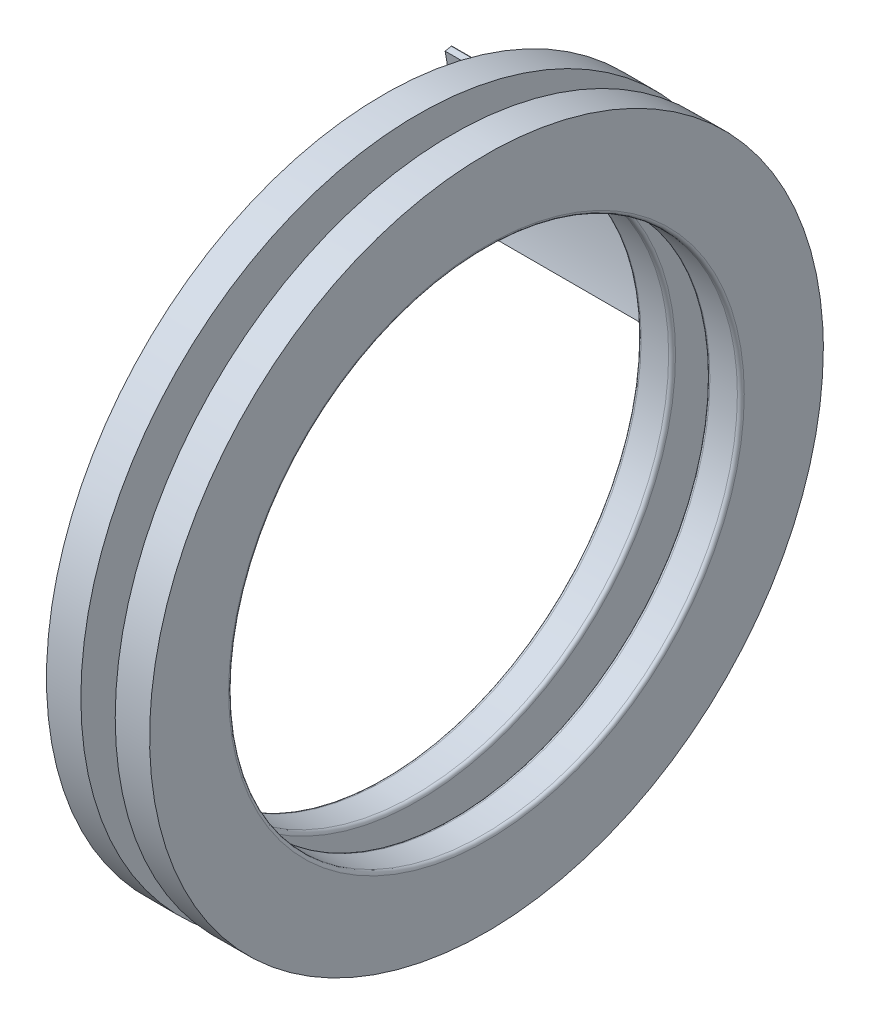
SolidWorks part; units mm, degrees
ref_plane "Front Plane" through (0, 0, 0) normal (0, 0, 1) x (1, 0, 0)
ref_plane "Top Plane" through (0, 0, 0) normal (0, 1, 0) x (1, 0, 0)
ref_plane "Right Plane" through (0, 0, 0) normal (1, 0, 0) x (0, 0, -1)
sketch "airflap" plane through (0, 0, 0) normal (1, 0, 0) x (0, 0, -1)
  line L0 (0, 0) -> (0, 50) construction
  line L1 (0, 0) -> (0, -50) construction
  line L2 (49.9696, 10.2) -> (48.9898, 10)
  line L3 (-48.9898, -10) -> (48.9898, -10) construction
  line L4 (-48.9898, -10) -> (-48.9898, 10) construction
  line L5 (-48.9898, 10) -> (48.9898, 10) construction
  line L6 (48.9898, -10) -> (48.9898, 10) construction
  line L7 (-48.9898, -10) -> (48.9898, 10) construction
  line L8 (-48.9898, 10) -> (48.9898, -10) construction
  line L9 (48.9898, -10) -> (49.9696, -10.2)
  arc A0 (48.9898, 10) -> (48.9898, -10) centre (0, 0) cw
  arc A1 (49.9696, 10.2) -> (49.9696, -10.2) centre (0, 0) cw
  dimension "D2" = 20
  dimension "D3" = 50
  dimension "D4" = 51
  dimension "D1" = 50
extrude "Boss-Extrude1" add sketch "airflap" along normal blind 50
fillet "Fillet3" radius 0.1 5 edges at (50, 10.1, -49.4797) (50, -10.1, -49.4797) (25, -10.2, -49.9696) (25, 10.2, -49.9696) (50, 0, -51)
ref_plane "hinge sketch" through (50, 0, 0) normal (1, 0, 0) x (0, 0, -1)
sketch "inner-hinge" plane through (50, 0, 0) normal (1, 0, 0) x (0, 0, -1)
  line L0 (49.0097, 9.902) -> (49.0097, -9.902) construction
  line L1 (49.0097, 0) -> (50, 0) construction
  line L2 (49.0097, 3) -> (42.0097, 3)
  line L4 (49.0097, -3) -> (42.0097, -3)
  line L5 (42.0097, 3) -> (42.0097, -3)
  line L6 (49.0097, 3) -> (49.9099, 3)
  line L8 (49.0097, -3) -> (49.9099, -3)
  line L9 (49.0097, 0) -> (42.0097, 0) construction
  arc A0 (49.0097, -9.902) -> (49.0097, 9.902) centre (0, 0) ccw construction
  arc A1 (49.9099, 3) -> (49.9099, -3) centre (0, 0) cw
  dimension "D1" = 6
  dimension "D2" = 42.0097
  dimension "D3" = 7
  dimension "D5" = 0.9903
extrude "Boss-Extrude2" add sketch "inner-hinge" against normal blind 5 separate body
ref_plane "inner-screw hinge" through (0, 0, 0) normal (0, 1, 0) x (1, 0, 0)
sketch "cutout-hinge" plane through (0, 0, 0) normal (0, 1, 0) x (1, 0, 0)
  line L0 (47.5, 42.0097) -> (47.5, 50) construction
  line L1 (45, 42.0097) -> (50, 42.0097) construction
  line L2 (45, 42.0097) -> (50, 42.0097) construction
  line L3 (45, 42.0097) -> (45, 49.9099) construction
  line L4 (50, 42.0097) -> (45, 42.0097)
  line L5 (50, 42.0097) -> (50, 48.9898)
  line L6 (50, 48.9898) -> (45, 48.9898)
  line L7 (45, 42.0097) -> (45, 48.9898)
  line L8 (49.9, 48.9898) -> (0, 48.9898) construction
  circle A0 centre (47.5, 46.0048) radius 2
  circle A1 centre (47.5, 46.0048) radius 2.5
  dimension "D1" = 4
  dimension "D2" = 7.9903
  dimension "D3" = 3.9952
  dimension "D4" = 0.5
fillet "Fillet4" radius 0.5 2 edges at (50, 0, -42.0097) (45, 0, -42.0097)
sketch "set ring" plane through (50, 0, 0) normal (1, 0, 0) x (0, 0, -1)
  circle A0 centre (0, 0) radius 49.0097
  circle A1 centre (0, 0) radius 37.0097
  dimension "D1" = 12
extrude "setring" add sketch "set ring" along normal blind 5
ref_plane "mirrorplane" through (47.5, 0, 0) normal (1, 0, 0) x (0, 0, -1)
mirror "Mirror1" about plane through (47.5, 0, 0) normal (1, 0, 0) of "setring"
fillet "Fillet5" radius 0.5 4 edges at (40, 0, -37.0097) (45, 0, -37.0097) (50, 0, -37.0097) (55, 0, -37.0097)
sketch "center line" plane through (0, 0, 0) normal (0, 0, 1) x (1, 0, 0)
  line L0 (79.34, 0) -> (-18.7746, 0) construction
extrude "Cut-Extrude1" cut sketch "cutout-hinge" against normal through all both and the other way through all contours L0 L4 L5 A1 | L4 L0 A1 L7 | A0 L0 | L0 A0 region at (46.0674, 0, -43.1022) region at (48.9326, 0, -43.1022) region at (46.6512, 0, -46.0048) region at (48.3488, 0, -46.0048)
equation "\"D3@cutout-hinge\" = \"D2@cutout-hinge\" / 2"
